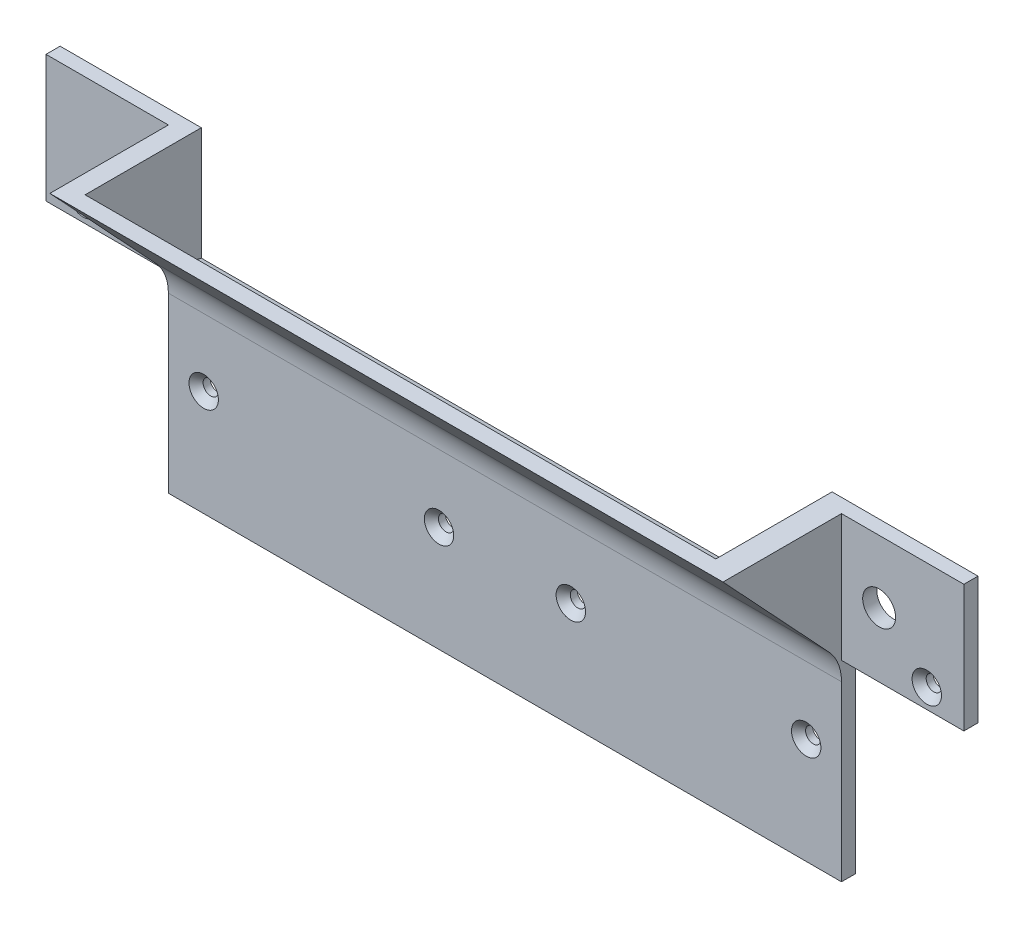
SolidWorks part; units mm, degrees
ref_plane "Alzado" through (0, 0, 0) normal (0, 0, 1) x (1, 0, 0)
ref_plane "Planta" through (0, 0, 0) normal (0, 1, 0) x (1, 0, 0)
ref_plane "Vista lateral" through (0, 0, 0) normal (1, 0, 0) x (0, 0, -1)
sketch "Croquis1" plane through (0, 0, 0) normal (0, 0, 1) x (1, 0, 0)
  line L0 (-97.5, -1.75) -> (-97.5, -25.75)
  line L1 (-97.5, -25.75) -> (-71.5, -25.75)
  line L2 (-71.5, -25.75) -> (-71.5, -66.5)
  line L3 (-71.5, -66.5) -> (71.5, -66.5)
  line L4 (-97.5, -1.75) -> (97.5, -1.75)
  line L5 (0, -66.5) -> (0, 0) construction
  line L6 (71.5, -25.75) -> (71.5, -66.5)
  line L7 (97.5, -25.75) -> (71.5, -25.75)
  line L8 (97.5, -1.75) -> (97.5, -25.75)
  circle A0 centre (-89.62, -21.62) radius 1.625
  circle A1 centre (-64, -44) radius 1.625
  circle A2 centre (-14, -44) radius 1.625
  circle A3 centre (14, -44) radius 1.625
  circle A4 centre (64, -44) radius 1.625
  circle A5 centre (89.62, -21.62) radius 1.625
  dimension "D3" = 4.13
  dimension "D4" = 3.25
  dimension "D5" = 7.88
  dimension "D9" = 50
  dimension "D11" = 3.25
  dimension "D12" = 26
  dimension "D1" = 40.75
  dimension "D2" = 24
  dimension "D6" = 33.5
  dimension "D7" = 7.5
  dimension "D8" = 71.5
  dimension "D10" = 22.5
extrude "Saliente-Extruir1" add sketch "Croquis1" along normal blind 3
sketch "Croquis2" plane through (0, 0, 3) normal (0, 0, 1) x (1, 0, 0)
  line L0 (97.5, -1.75) -> (-97.5, -1.75) construction
  line L1 (-71.5, -25.75) -> (71.5, -25.75)
  line L2 (-71.5, -25.75) -> (-71.5, -1.75)
  line L3 (-71.5, -1.75) -> (71.5, -1.75)
  line L4 (71.5, -25.75) -> (71.5, -1.75)
  line L5 (71.5, -66.5) -> (71.5, -25.75) construction
extrude "Saliente-Extruir2" add sketch "Croquis2" along normal blind 13
sketch "Croquis4" plane through (-71.5, 0, 0) normal (-1, 0, 0) x (0, 0, 1)
  line L0 (0, -22.75) -> (12.2544, -19.75)
  line L1 (0, -1.75) -> (0, -25.75) construction
  line L2 (12.2544, -19.75) -> (12.2544, -7.75)
  line L3 (12.2544, -7.75) -> (0, -4.75)
  line L4 (0, -4.75) -> (0, -22.75)
  line L5 (16, -25.75) -> (3, -25.75) construction
  line L6 (16, -1.75) -> (3, -1.75) construction
  dimension "D1" = 3
  dimension "D2" = 6
  dimension "D3" = 3
  dimension "D4" = 6
extrude "Cortar-Extruir1" cut sketch "Croquis4" against normal blind 134 from offset 4 offset against normal yes
sketch "Croquis5" plane through (-71.5, 0, 0) normal (-1, 0, 0) x (0, 0, 1)
  line L0 (3, -25.75) -> (16, -22.5675)
  line L1 (16, -22.5675) -> (16, -5.6669)
  line L2 (16, -5.6669) -> (0, -1.75)
  line L3 (0, -1.75) -> (13.1267, 3.4111)
  line L4 (13.1267, 3.4111) -> (22.4909, -3.1113)
  line L5 (22.4909, -3.1113) -> (22.4909, -28.233)
  line L8 (0, -22.75) -> (12.2544, -19.75) construction
  line L9 (12.2544, -7.75) -> (0, -4.75) construction
  line L10 (3, -25.75) -> (22.4909, -28.233)
  line L11 (16, -1.75) -> (16, -25.75) construction
  dimension "D1" = 2.483
extrude "Cortar-Extruir2" cut sketch "Croquis5" against normal through all both and the other way through all
sketch "Croquis6" plane through (0, 0, 16) normal (0, 0, 1) x (1, 0, 0)
  line L0 (-71.5, -20.0675) -> (71.5, -20.0675) construction
  line L1 (-71.5, -5.6669) -> (-71.5, -22.5675) construction
  line L2 (71.5, -22.5675) -> (71.5, -5.6669) construction
  line L3 (-71.5, -22.5675) -> (71.5, -22.5675) construction
  text T0 "<b><i>      RYO</i></b>" font "Century Gothic" height 12
  dimension "D1" = 2.5
extrude "Saliente-Extruir3" add sketch "Croquis6" along normal blind 1
chamfer "Chaflán1" distance 1.5 angle 45 6 edges at (-87.995, -21.62, 3) (87.995, -21.62, 3) (62.375, -44, 3) (12.375, -44, 3) (-12.375, -44, 3) (-62.375, -44, 3)
sketch "Croquis7" plane through (0, 0, 3) normal (0, 0, 1) x (1, 0, 0)
  line L0 (-71.5, -25.75) -> (71.5, -25.75) construction
  circle A0 centre (0, -33.75) radius 6
  dimension "D1" = 12
  dimension "D2" = 8
extrude "Cortar-Extruir3" cut sketch "Croquis7" against normal blind 10
sketch "Croquis11" plane through (0, 0, 3) normal (0, 0, 1) x (1, 0, 0)
  line L0 (0, 0) -> (0, 47.0371) construction
  line L1 (-71.5, -5.6669) -> (-71.5, -22.5675) construction
  circle A0 centre (-79.5, -12.1) radius 5
  circle A1 centre (79.5, -12.1) radius 5
  dimension "D1" = 10
  dimension "D2" = 8
extrude "Cortar-Extruir7" cut sketch "Croquis11" against normal blind 60
sketch "Croquis12" plane through (71.5, 0, 0) normal (1, 0, 0) x (0, 0, -1)
  line L1 (-3, -25.75) -> (-42.7545, -25.75)
  line L2 (-3, -25.75) -> (-3, 2.1699)
  line L3 (-3, 2.1699) -> (-42.7545, 2.1699)
  line L4 (-42.7545, -25.75) -> (-42.7545, 2.1699)
extrude "Cortar-Extruir8" cut sketch "Croquis12" against normal through all both and the other way through all
sketch "Croquis13" plane through (0, 0, 3) normal (0, 0, 1) x (1, 0, 0)
  line L0 (97.5, -1.75) -> (-97.5, -1.75) construction
  line L1 (-67.5, -5.4844) -> (66.6179, -5.4844)
  line L2 (-67.5, -5.4844) -> (-67.5, -1.75)
  line L3 (-67.5, -1.75) -> (66.6179, -1.75)
  line L4 (66.6179, -5.4844) -> (66.6179, -1.75)
extrude "Cortar-Extruir9" cut sketch "Croquis13" against normal through all both and the other way through all
sketch "Croquis14" plane through (97.5, 0, 0) normal (1, 0, 0) x (0, 0, -1)
  line L1 (-3, -2.4844) -> (1.0696, -2.4844)
  line L2 (-3, -2.4844) -> (-3, 1.7401)
  line L3 (-3, 1.7401) -> (1.0696, 1.7401)
  line L4 (1.0696, -2.4844) -> (1.0696, 1.7401)
extrude "Cortar-Extruir10" cut sketch "Croquis14" against normal through all both and the other way through all
sketch "Croquis22" plane through (0, 0, 3) normal (0, 0, 1) x (1, 0, 0)
  line L0 (71.5, -25.75) -> (97.5, -25.75) construction
  line L1 (66.5, -5.4844) -> (97.5, -5.4844)
  line L2 (66.5, -5.4844) -> (66.5, 1.25)
  line L3 (66.5, 1.25) -> (97.5, 1.25)
  line L4 (97.5, -5.4844) -> (97.5, 1.25)
  line L5 (0, 0) -> (0, -86.3709) construction
  line L6 (-97.5, -5.4844) -> (-97.5, 1.25)
  line L7 (-66.5, 1.25) -> (-97.5, 1.25)
  line L8 (-66.5, -5.4844) -> (-66.5, 1.25)
  line L9 (-66.5, -5.4844) -> (-97.5, -5.4844)
  dimension "D1" = 27
extrude "Saliente-Extruir9" add sketch "Croquis22" against normal up to surface (3 mm away) up to face at (9.374, -21.6005, 0)
sketch "Croquis23" plane through (0, 0, 3) normal (0, 0, 1) x (1, 0, 0)
  line L1 (-67.5, -5.4844) -> (-52.3616, -5.4844)
  line L2 (-67.5, -5.4844) -> (-67.5, 28.6678)
  line L3 (-67.5, 28.6678) -> (-52.3616, 28.6678)
  line L4 (-52.3616, -5.4844) -> (-52.3616, 28.6678)
extrude "Cortar-Extruir11" cut sketch "Croquis23" against normal blind 10
sketch "Croquis15" plane through (71.5, 0, 0) normal (1, 0, 0) x (0, 0, -1)
  line L0 (-3, -25.75) -> (-28.1752, 1.25)
  line L1 (-28.1752, 1.25) -> (-3, 1.25)
  line L2 (-3, 1.25) -> (-3, -25.75)
extrude "Saliente-Extruir4" add sketch "Croquis15" against normal up to vertex (5 mm away) up to point (66.5, -22.0156, 3)
sketch "Croquis16" plane through (-71.5, 0, 0) normal (-1, 0, 0) x (0, 0, 1)
  line L0 (3, 1.25) -> (28.1752, 1.25)
  line L1 (28.1752, 1.25) -> (3, -25.75)
  line L2 (3, -25.75) -> (3, 1.25)
extrude "Saliente-Extruir5" add sketch "Croquis16" against normal up to vertex (4 mm away) up to point (-67.5, -22.0156, 3)
sketch "Croquis17" plane through (-71.5, 0, 0) normal (-1, 0, 0) x (0, 0, 1)
  line L0 (3, -22.0156) -> (24.6931, 1.25)
  line L2 (24.6931, 1.25) -> (28.1752, 1.25)
  line L3 (28.1752, 1.25) -> (3, -25.75)
  line L4 (3, -25.75) -> (3, -22.0156)
  line L5 (3, -25.75) -> (28.1752, 1.25) construction
extrude "Saliente-Extruir6" add sketch "Croquis17" against normal up to surface (143 mm away) from surface up to face at (71.5, -7.75, 11.3917) starting at face at (-67.5, -13.6031, 6.835)
sketch "Croquis18" plane through (0, 0, 3) normal (0, 0, 1) x (1, 0, 0)
  circle A0 centre (0, -33.75) radius 6
extrude "Saliente-Extruir7" add sketch "Croquis18" against normal up to surface (3 mm away) up to face at (-0.1667, -23.0417, 0)
fillet "Redondeo1" radius 10 1 edges at (0, -25.75, 3)
sketch "Croquis19" plane through (0, 0, 3) normal (0, 0, 1) x (1, 0, 0)
  circle A0 centre (-79.5, -12.1) radius 3.25
  circle A1 centre (-79.5, -12.1) radius 5
  circle A2 centre (79.5, -12.1) radius 3.5
  circle A3 centre (79.5, -12.1) radius 5
  dimension "D1" = 6.5
  dimension "D2" = 7
extrude "Saliente-Extruir8" add sketch "Croquis19" against normal up to surface (3 mm away) up to face at (-0.1667, -23.0417, 0)
sketch "Croquis24" plane through (0, 0, 0) normal (1, 0, 0) x (0, 0, -1)
sketch "Croquis25" plane through (-67.5, 0, 0) normal (1, 0, 0) x (0, 0, -1)
  line L3 (0, 1.25) -> (0, -22.75) construction
  line L4 (-24.6931, 1.25) -> (-3, -22.0156) construction
  arc A0 (0, -17.5469) -> (-4.5936, -20.3065) centre (0, -22.75) ccw
